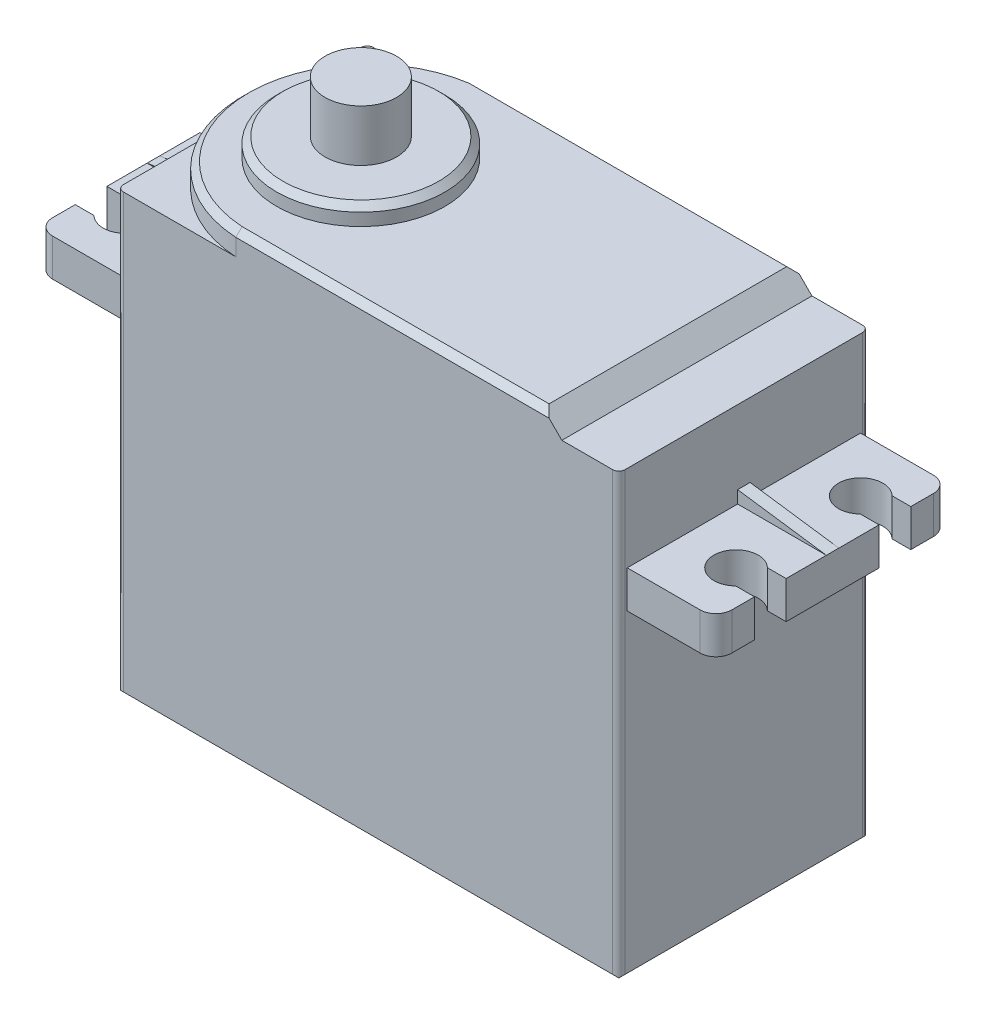
SolidWorks part; units mm, degrees
ref_plane "Front Plane" through (0, 0, 0) normal (0, 0, 1) x (1, 0, 0)
ref_plane "Top Plane" through (0, 0, 0) normal (0, 1, 0) x (1, 0, 0)
ref_plane "Right Plane" through (0, 0, 0) normal (1, 0, 0) x (0, 0, -1)
sketch "Sketch1" plane through (0, 0, 0) normal (0, 1, 0) x (1, 0, 0)
  line L1 (-20.1295, -10.033) -> (20.1295, -10.033)
  line L2 (-20.1295, -10.033) -> (-20.1295, 10.033)
  line L3 (-20.1295, 10.033) -> (20.1295, 10.033)
  line L4 (20.1295, -10.033) -> (20.1295, 10.033)
  line L5 (-20.1295, -10.033) -> (20.1295, 10.033) construction
  line L6 (-20.1295, 10.033) -> (20.1295, -10.033) construction
  point P0 (0, 0)
  dimension "D1" = 20.066
  dimension "D2" = 40.259
extrude "Boss-Extrude1" add sketch "Sketch1" along normal blind 38.1
ref_plane "Plane1" through (0, 26.67, 0) normal (0, -1, 0) x (-1, 0, 0)
sketch "Sketch2" plane through (0, 26.67, 0) normal (0, -1, 0) x (-1, 0, 0)
  line L1 (27.25, -9.3599) -> (-27.25, -9.3599)
  line L2 (27.25, -9.3599) -> (27.25, 9.3599)
  line L3 (27.25, 9.3599) -> (-27.25, 9.3599)
  line L4 (-27.25, -9.3599) -> (-27.25, 9.3599)
  line L5 (27.25, -9.3599) -> (-27.25, 9.3599) construction
  line L6 (27.25, 9.3599) -> (-27.25, -9.3599) construction
  point P0 (0, 0)
  dimension "D1" = 18.7198
  dimension "D2" = 54.5
extrude "Boss-Extrude2" add sketch "Sketch2" against normal blind 2.9972
sketch "Sketch3" plane through (0, 38.1, 0) normal (0, 1, 0) x (1, 0, 0)
  line L0 (-20.1295, 10.033) -> (-20.1295, -10.033) construction
  circle A0 centre (-10.6045, 0) radius 2.8702
  dimension "D2" = 5.7404
  dimension "D1" = 9.525
extrude "Boss-Extrude3" add sketch "Sketch3" along normal blind 5.6388
sketch "Sketch4" plane through (0, 29.6672, 0) normal (0, 1, 0) x (1, 0, 0)
  line L0 (-35.4024, 0) -> (37.6199, 0) construction
  line L1 (0, 17.908) -> (0, -16.6827) construction
  circle A0 centre (-24.5, 5) radius 1.778
  circle A1 centre (-24.5, -5) radius 1.778
  circle A2 centre (24.5, -5) radius 1.778
  circle A3 centre (24.5, 5) radius 1.778
  dimension "D3" = 3.556
  dimension "D4" = 3.556
  dimension "D5" = 3.556
  dimension "D6" = 3.556
  dimension "D1" = 49
  dimension "D2" = 10
extrude "Cut-Extrude1" cut sketch "Sketch4" against normal through all
sketch "Sketch5" plane through (0, 29.6672, 0) normal (0, 1, 0) x (1, 0, 0)
  line L0 (-24.5, -5) -> (-36.94, -5) construction
  line L1 (24.5, 5) -> (34.8628, 5) construction
  line L2 (-24.5, 5) -> (-37.4141, 5) construction
  line L3 (24.5, -5) -> (35.3369, -5) construction
  line L5 (-32.12, 3.73) -> (-24.5, 3.73)
  line L6 (-32.12, 3.73) -> (-32.12, 6.27)
  line L7 (-32.12, 6.27) -> (-24.5, 6.27)
  line L8 (-24.5, 3.73) -> (-24.5, 6.27)
  line L9 (-32.12, 3.73) -> (-24.5, 6.27) construction
  line L10 (-32.12, 6.27) -> (-24.5, 3.73) construction
  line L11 (-30.85, -6.27) -> (-24.5, -6.27)
  line L12 (-30.85, -6.27) -> (-30.85, -3.73)
  line L13 (-30.85, -3.73) -> (-24.5, -3.73)
  line L14 (-24.5, -6.27) -> (-24.5, -3.73)
  line L15 (-30.85, -6.27) -> (-24.5, -3.73) construction
  line L16 (-30.85, -3.73) -> (-24.5, -6.27) construction
  line L17 (30.85, 3.73) -> (24.5, 3.73)
  line L18 (30.85, 3.73) -> (30.85, 6.27)
  line L19 (30.85, 6.27) -> (24.5, 6.27)
  line L20 (24.5, 3.73) -> (24.5, 6.27)
  line L21 (30.85, 3.73) -> (24.5, 6.27) construction
  line L22 (30.85, 6.27) -> (24.5, 3.73) construction
  line L23 (30.85, -6.27) -> (24.5, -6.27)
  line L24 (30.85, -6.27) -> (30.85, -3.73)
  line L25 (30.85, -3.73) -> (24.5, -3.73)
  line L26 (24.5, -6.27) -> (24.5, -3.73)
  line L27 (30.85, -6.27) -> (24.5, -3.73) construction
  line L28 (30.85, -3.73) -> (24.5, -6.27) construction
  point P2 (-28.31, 5)
  point P17 (-27.675, -5)
  point P22 (27.675, 5)
  point P27 (27.675, -5)
  dimension "D1" = 7.62
  dimension "D2" = 6.35
  dimension "D3" = 2.54
  dimension "D4" = 2.54
  dimension "D5" = 6.35
  dimension "D6" = 6.35
  dimension "D7" = 2.54
  dimension "D8" = 2.54
extrude "Cut-Extrude2" cut sketch "Sketch5" against normal through all
fillet "Fillet2" radius 1.27 4 edges at (27.25, 28.1686, -9.3599) (27.25, 28.1686, 9.3599) (-27.25, 28.1686, 9.3599) (-27.25, 28.1686, -9.3599)
sketch "Sketch6" plane through (-20.1295, 0, 0) normal (-1, 0, 0) x (0, 0, 1)
  line L0 (-10.033, 0) -> (10.033, 0) construction
  line L1 (-3.6195, 7.874) -> (3.6195, 7.874)
  line L2 (-3.6195, 7.874) -> (-3.6195, 3.556)
  line L3 (-3.6195, 3.556) -> (3.6195, 3.556)
  line L4 (3.6195, 7.874) -> (3.6195, 3.556)
  line L5 (-3.6195, 7.874) -> (3.6195, 3.556) construction
  line L6 (-3.6195, 3.556) -> (3.6195, 7.874) construction
  line L7 (0, 0) -> (0, 13.3979) construction
  point P0 (0, 5.715)
  dimension "D1" = 3.556
  dimension "D2" = 4.318
  dimension "D3" = 7.239
extrude "Boss-Extrude4" add sketch "Sketch6" along normal blind 5.08 draft 5
sketch "Sketch7" plane through (0, 38.1, 0) normal (0, 1, 0) x (1, 0, 0)
  line L0 (20.1295, 10.033) -> (-20.1295, 10.033) construction
  line L1 (20.1295, -10.033) -> (15.5575, -10.033)
  line L2 (20.1295, -10.033) -> (20.1295, 10.033)
  line L3 (20.1295, 10.033) -> (15.5575, 10.033)
  line L4 (15.5575, -10.033) -> (15.5575, 10.033)
  dimension "D1" = 4.572
extrude "Cut-Extrude3" cut sketch "Sketch7" against normal blind 1.524
chamfer "Chamfer1" distance 1.524 angle 45 1 edges at (15.5575, 38.1, 0)
sketch "Sketch8" plane through (0, 38.1, 0) normal (0, 1, 0) x (1, 0, 0)
  line L0 (-10.6045, 20.2431) -> (-10.6045, 0) construction
  line L1 (-10.6045, 10.1215) -> (-31.4314, 17.8122)
  line L2 (-10.6045, 0) -> (-32.3007, 0) construction
  line L3 (-31.4314, 17.8122) -> (-23.5267, -15.8682)
  line L4 (-10.6045, 0) -> (-10.6045, -17.0893) construction
  line L5 (0, 10.033) -> (-28.1984, 10.033) construction
  line L6 (14.0335, 10.033) -> (-20.1295, 10.033) construction
  line L7 (4.8815, -10.033) -> (-38.0382, -10.033) construction
  line L8 (-20.1295, -10.033) -> (14.0335, -10.033) construction
  line L9 (-20.1295, 10.033) -> (-20.1295, -10.033) construction
  line L10 (-23.5267, -15.8682) -> (-10.6045, -10.033)
  arc A0 (-10.6045, 10.1215) -> (-10.6045, -10.033) centre (-10.0362, 0.0443) ccw
  point P10 (-10.6045, -10.033)
  point P13 (-10.6045, 10.033)
  point P18 (-20.1295, 0)
extrude "Cut-Extrude4" cut sketch "Sketch8" against normal blind 1.8542
sketch "Sketch9" plane through (0, 38.1, 0) normal (0, 1, 0) x (1, 0, 0)
  line L0 (-10.6045, -6.75) -> (-10.6045, 6.75) construction
  line L1 (-17.3545, 0) -> (-3.8545, 0) construction
  circle A0 centre (-10.6045, 0) radius 6.75
  dimension "D1" = 13.5
extrude "Boss-Extrude5" add sketch "Sketch9" along normal blind 1.5
chamfer "Chamfer2" distance 0.5 angle 45 4 edges at (1.2742, 38.1, -10.033) (1.7145, 38.1, 10.033) (-20.1198, 38.1, 0.3983) (-10.6045, 39.6, 6.75) tangent propagation no
chamfer "Chamfer3" distance 1.5 angle 45 4 edges at (0, 0, -10.033) (-20.1295, 0, 0) (0, 0, 10.033) (20.1295, 0, 0)
fillet "Fillet3" radius 0.5 4 edges at (-20.1295, 18.8729, -10.033) (-20.1295, 18.8729, 10.033) (20.1295, 19.038, 10.033) (20.1295, 19.038, -10.033)
sketch "Sketch12" plane through (0, 0, 0) normal (0, 0, 1) x (1, 0, 0)
  line L0 (-27.25, 29.6672) -> (-20.1295, 29.6672)
  line L1 (-20.1295, 29.6672) -> (-20.1295, 30.6672)
  line L2 (-20.1295, 1.5) -> (-20.1295, 36.2458) construction
  line L3 (-20.1295, 30.6672) -> (-27.25, 29.6672)
  dimension "D1" = 1
extrude "Boss-Extrude6" add sketch "Sketch12" along normal blind 0.5 and the other way blind 0.5
mirror "Mirror1" about plane through (0, 0, 0) normal (1, 0, 0) of "Boss-Extrude6"
fillet "Fillet4" radius 1 8 edges at (-25.2095, 4.0004, 0) (-25.2095, 5.715, -3.1751) (-25.2095, 7.4296, 0) (-25.2095, 5.715, 3.1751) (-22.6695, 7.6518, -3.3973) (-22.6695, 7.6518, 3.3973) (-22.6695, 3.7782, -3.3973) (-22.6695, 3.7782, 3.3973) tangent propagation no
